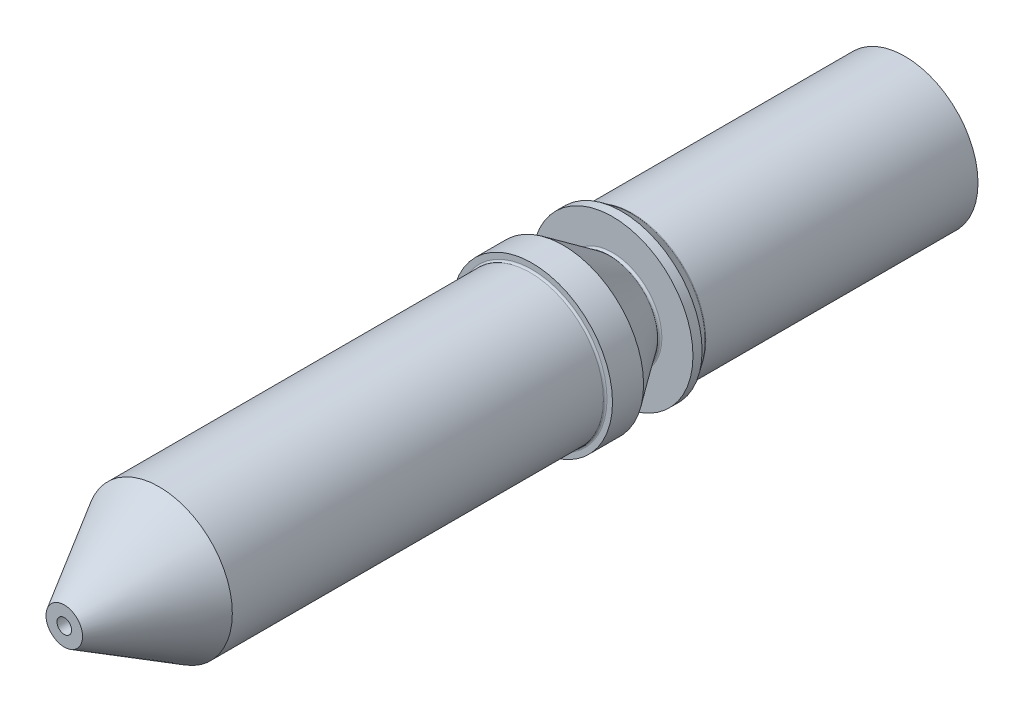
SolidWorks part; units mm, degrees
material "AISI Type 316L stainless steel"
ref_plane "Front Plane" through (0, 0, 0) normal (0, 0, 1) x (1, 0, 0)
ref_plane "Top Plane" through (0, 0, 0) normal (0, 1, 0) x (1, 0, 0)
ref_plane "Right Plane" through (0, 0, 0) normal (1, 0, 0) x (0, 0, -1)
sketch "Sketch1" plane through (0, 0, 0) normal (0, 1, 0) x (1, 0, 0)
  line L0 (0.5, -23) -> (2, -20.4019)
  line L1 (2, -20.4019) -> (2, -10.25)
  line L2 (0.5, -22.4197) -> (0.5, -21.8)
  line L3 (0.5, -21.8) -> (1, -21.4996)
  line L4 (2.2, -9.3498) -> (1.309, -8.0774)
  line L5 (1.35, -7.9987) -> (2.2, -7.9987)
  line L6 (2, -7.4473) -> (2, 0)
  line L7 (2.05, -10.2) -> (2.2, -10.2)
  line L8 (2.2, -10.2) -> (2.2, -9.3498)
  line L9 (2.009, -7.476) -> (2.2, -7.7487)
  line L10 (2.2, -7.7487) -> (2.2, -7.9987)
  line L11 (1, 0) -> (1, -21.4996)
  line L12 (0.5, -22.4197) -> (0.2, -22.6)
  line L13 (0.2, -22.6) -> (0.2, -23)
  line L14 (0.2, -23) -> (0.5, -23)
  line L15 (0, 0) -> (0, -33.6776) construction
  line L16 (1, 0) -> (2, 0)
  arc A0 (1.309, -8.0774) -> (1.35, -7.9987) centre (1.35, -8.0487) cw
  arc A1 (2, -10.25) -> (2.05, -10.2) centre (2.05, -10.25) cw
  arc A2 (2, -7.4473) -> (2.009, -7.476) centre (2.05, -7.4473) ccw
  point P9 (1.3, -8.0487)
  dimension "D10" = 0.05
  dimension "D17" = 0.25
  dimension "D2" = 4
  dimension "D3" = 31
  dimension "D4" = 1.2
  dimension "D5" = 0.4
  dimension "D6" = 60
  dimension "D7" = 1
  dimension "D8" = 15.0013
  dimension "D9" = 55
  dimension "D11" = 2.6
  dimension "D12" = 2
  dimension "D13" = 23
  dimension "D14" = 0.4
  dimension "D15" = 1
  dimension "D16" = 12.8
  dimension "D18" = 4.4
revolve "Revolve1" add sketch "Sketch1" angle 360 about L15 reverse direction yes
cosmetic thread "Cosmetic Thread1" parameters "D1"=11.8, "D2"=3.22
cosmetic thread "Cosmetic Thread2" parameters "D1"=7.5, "D2"=3.22
